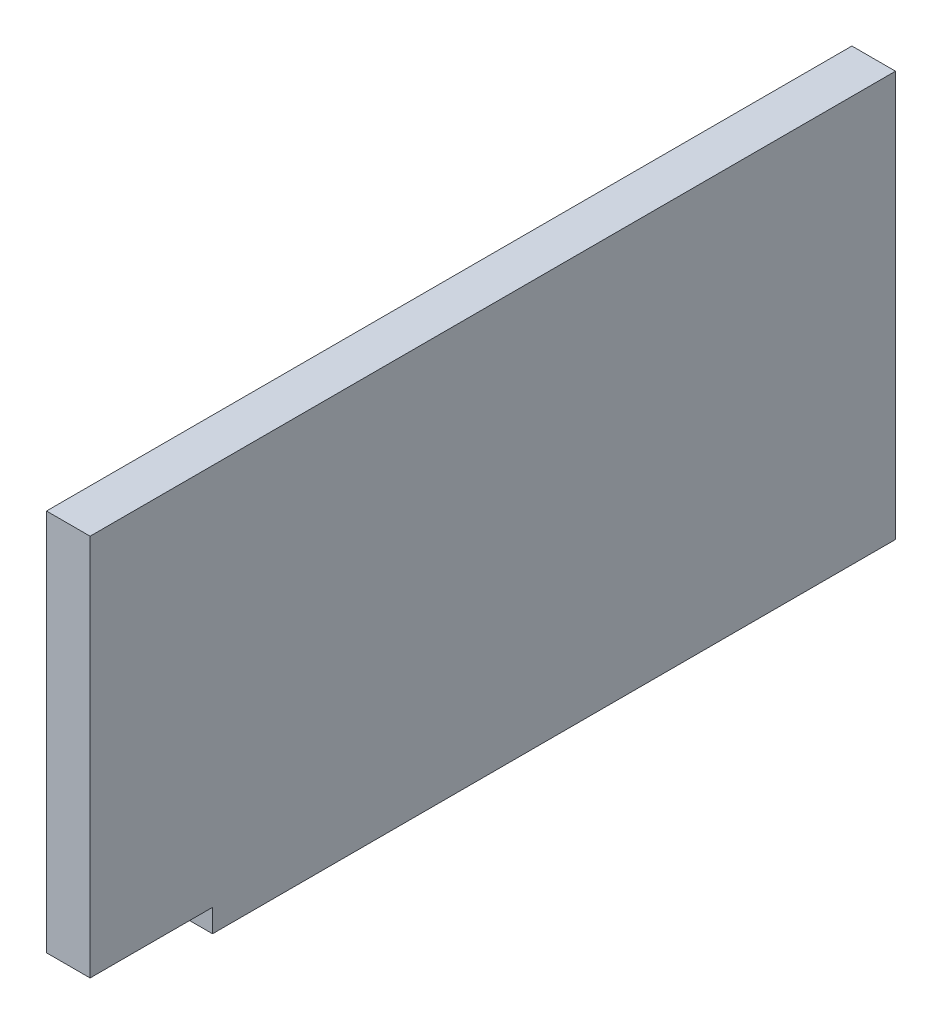
SolidWorks part; units mm, degrees
ref_plane "Front Plane" through (0, 0, 0) normal (0, 0, 1) x (1, 0, 0)
ref_plane "Top Plane" through (0, 0, 0) normal (0, 1, 0) x (1, 0, 0)
ref_plane "Right Plane" through (0, 0, 0) normal (1, 0, 0) x (0, 0, -1)
sketch "Sketch1" plane through (0, 0, 0) normal (1, 0, 0) x (0, 0, -1)
  line L1 (-52.625, 26.5) -> (52.625, 26.5)
  line L2 (-52.625, 26.5) -> (-52.625, -26.5)
  line L3 (-52.625, -26.5) -> (52.625, -26.5)
  line L4 (52.625, 26.5) -> (52.625, -26.5)
  point P4 (0, 26.5)
  point P5 (52.625, 0)
  dimension "D1" = 105.25
  dimension "D2" = 53
extrude "Boss-Extrude1" add sketch "Sketch1" along normal blind 2.85 and the other way blind 2.85 contours L2 L3 L4 L1
sketch "Sketch2" plane through (2.85, 0, 0) normal (1, 0, 0) x (0, 0, -1)
  line L0 (-52.625, -26.5) -> (52.625, -26.5) construction
  line L1 (-52.625, -26.5) -> (-36.625, -26.5)
  line L2 (-52.625, -26.5) -> (-52.625, -23.5)
  line L3 (-52.625, -23.5) -> (-36.625, -23.5)
  line L4 (-36.625, -26.5) -> (-36.625, -23.5)
  dimension "D1" = 16
  dimension "D2" = 3
  dimension "D3" = 0
extrude "Cut-Extrude1" cut sketch "Sketch2" against normal through all
equation "\"RoomSize\"= 100mm"
equation "\"D1@Sketch1\"=(\"RoomSize\"+\"WallsThick\")-\"WallsThick\"/8"
equation "\"RoomHeight\"= 5cm"
equation "\"D2@Sketch1\"=\"RoomHeight\"+\"CoverThick\""
equation "\"WallsThick\"= 6mm"
equation "\"D1@Boss-Extrude1\"=(0.95*\"WallsThick\")/2"
equation "\"D2@Boss-Extrude1\"=(0.95*\"WallsThick\")/2"
equation "\"HoleHeight\"= 3mm"
equation "\"D1@Sketch2\"=\"HoleWidth\"+\"WallsThick\"/2"
equation "\"D2@Sketch2\"= \"HoleHeight\""
equation "\"D3@Sketch2\"=\"HoleOffSet\""
equation "\"CoverThick\"= \"WallsThick\"/2"
equation "\"HoleWidth\"= 13mm"
equation "\"MeasureHoleSize\"= 3mm"
equation "\"ModelHeight\"= 1.7mm"
equation "\"HoleOffSet\"= 0"
